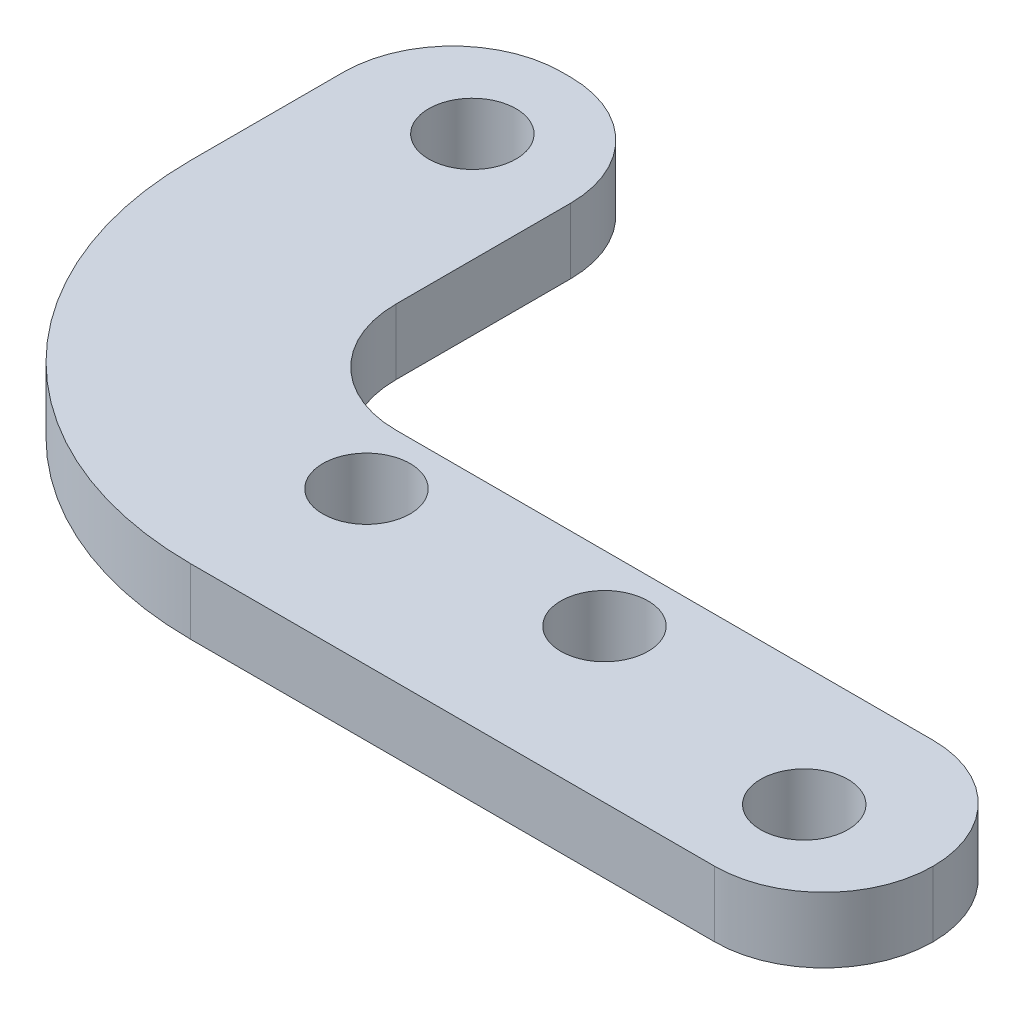
SolidWorks part; units mm, degrees
material "ABS PC"
ref_plane "Front Plane" through (0, 0, 0) normal (0, 0, 1) x (1, 0, 0)
ref_plane "Top Plane" through (0, 0, 0) normal (0, 1, 0) x (1, 0, 0)
ref_plane "Right Plane" through (0, 0, 0) normal (1, 0, 0) x (0, 0, -1)
sketch "Sketch1" plane through (0, 0, 0) normal (0, 1, 0) x (1, 0, 0)
  line L1 (22.5, -14) -> (-22.5, -14)
  line L2 (22.5, -14) -> (22.5, 14)
  line L3 (22.5, 14) -> (-22.5, 14)
  line L4 (-22.5, -14) -> (-22.5, 14)
  line L5 (22.5, -14) -> (-22.5, 14) construction
  line L6 (22.5, 14) -> (-22.5, -14) construction
  point P0 (0, 0)
  dimension "D1" = 28
  dimension "D2" = 45
extrude "Boss-Extrude1" add sketch "Sketch1" along normal blind 3
hole_wizard "Ø4.0 (4) Diameter Hole1" positions "Sketch2" profile "Sketch3" hole size "Ø4.0" standard "ANSI Metric" end condition through all
sketch "Sketch2" plane through (0, 3, 0) normal (0, 1, 0) x (1, 0, 0)
  line L1 (17.1, -9.5) -> (-17.1, -9.5)
  line L2 (17.1, -9.5) -> (17.1, 9.5)
  line L3 (17.1, 9.5) -> (-17.1, 9.5)
  line L4 (-17.1, -9.5) -> (-17.1, 9.5)
  line L5 (17.1, -9.5) -> (-17.1, 9.5) construction
  line L6 (17.1, 9.5) -> (-17.1, -9.5) construction
  line L7 (0, 14) -> (0, 0) construction
  line L8 (22.5, 14) -> (-22.5, 14) construction
  line L9 (0, 0) -> (0, -14) construction
  line L10 (-22.5, -14) -> (22.5, -14) construction
  point P2 (-17.1, 9.5)
  point P5 (17.1, -9.5)
  dimension "D1" = 19
  dimension "D2" = 34.2
sketch "Sketch3" plane through (-17.1, 3, -9.5) normal (1, 0, 0) x (0, 0, 1)
  line L0 (0, 0) -> (0, 3)
  line L1 (0, 3) -> (2, 3)
  line L2 (2, 3) -> (2, 0)
  line L5 (2, 0) -> (0, 0)
  line L11 (0, -6.35) -> (0, 107.95) construction
  dimension "Thru Hole Dia." = 4
  dimension "Thru Hole Depth" = 3
sketch "Sketch4" plane through (0, 3, 0) normal (0, 1, 0) x (1, 0, 0)
  line L0 (-22.5, -14) -> (22.5, -14) construction
  line L1 (9, -9) -> (-9, -9)
  line L2 (9, -9) -> (9, -14)
  line L3 (9, -14) -> (-9, -14)
  line L4 (-9, -9) -> (-9, -14)
  line L5 (9, -9) -> (-9, -14) construction
  line L6 (9, -14) -> (-9, -9) construction
  line L7 (0, -11.5) -> (0, 0) construction
  point P0 (0, -11.5)
  dimension "D1" = 18
  dimension "D2" = 5
extrude "Cut-Extrude1" [suppressed] cut sketch "Sketch4" against normal blind 3
hole_wizard "Ø4.0 (4) Diameter Hole2" positions "Sketch7" profile "Sketch8" hole size "Ø4.0" standard "ANSI Metric" end condition through all
sketch "Sketch7" plane through (0, 3, 0) normal (0, 1, 0) x (1, 0, 0)
  line L0 (0, 18.0075) -> (0, 15.2248) construction
  line L2 (-22.5, -14) -> (22.5, -14) construction
  point P0 (-5.45, -7)
  point P7 (5.45, -7)
  dimension "D1" = 10.9
  dimension "D2" = 7
sketch "Sketch8" plane through (-5.45, 3, 7) normal (1, 0, 0) x (0, 0, 1)
  line L0 (0, 0) -> (0, 3)
  line L1 (0, 3) -> (2, 3)
  line L2 (2, 3) -> (2, 0)
  line L5 (2, 0) -> (0, 0)
  line L11 (0, -6.35) -> (0, 107.95) construction
  dimension "Thru Hole Dia." = 4
  dimension "Thru Hole Depth" = 3
sketch "Sketch10" plane through (0, 3, 0) normal (0, 1, 0) x (1, 0, 0)
  line L0 (-12.1, 14) -> (-12.1, -4)
  line L1 (22.5, 14) -> (-22.5, 14) construction
  line L2 (-12.1, -4) -> (22.5, -4)
  line L3 (22.5, -14) -> (22.5, 14) construction
  line L4 (22.5, -4) -> (22.5, 14)
  line L5 (22.5, 14) -> (-12.1, 14)
  line L6 (-22.5, -14) -> (22.5, -14) construction
  circle A0 centre (-17.1, 9.5) radius 2 construction
  dimension "D1" = 5
  dimension "D2" = 10
extrude "Cut-Extrude2" cut sketch "Sketch10" against normal blind 3
fillet "Fillet2" radius 5 5 edges at (22.5, 1.5, 4) (22.5, 1.5, 14) (-22.5, 1.5, -14) (-12.1, 1.5, -14) (-12.1, 1.5, 4)
fillet "Fillet3" radius 16 1 edges at (-22.5, 1.5, 14)
